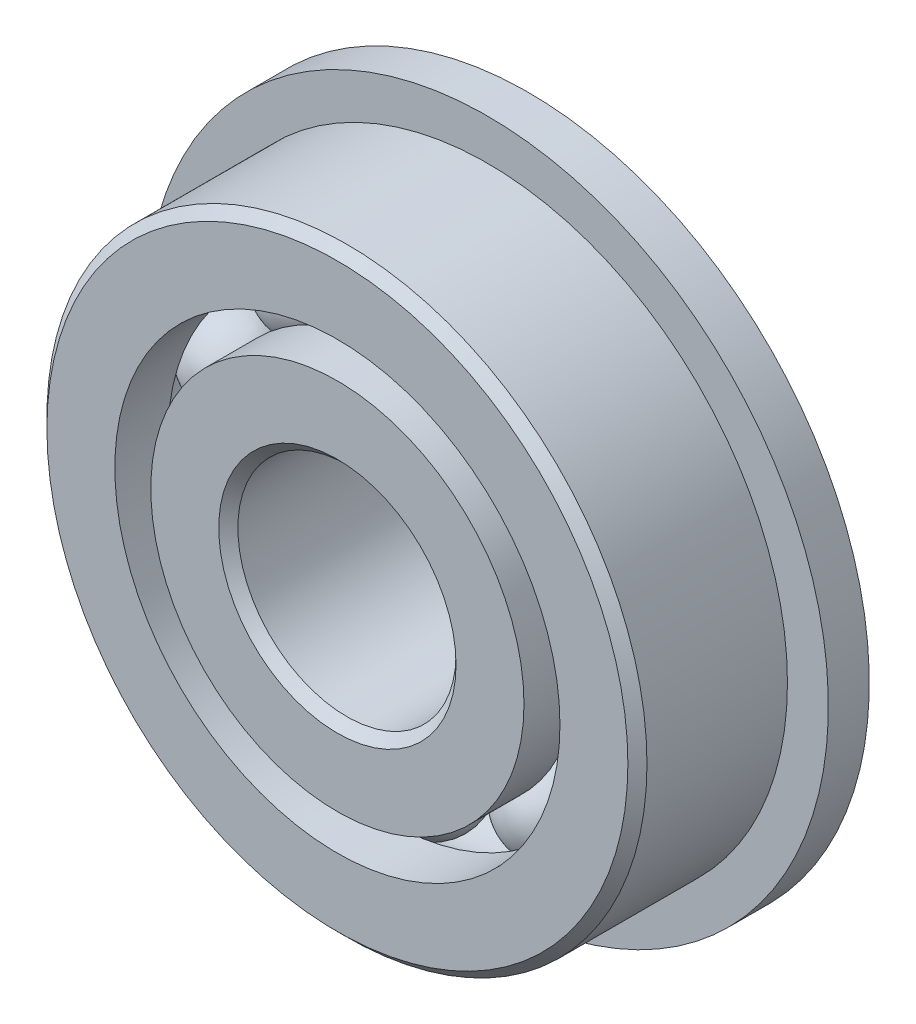
SolidWorks part; units mm, degrees
ref_plane "Front Plane" through (0, 0, 0) normal (0, 0, 1) x (1, 0, 0)
ref_plane "Top Plane" through (0, 0, 0) normal (0, 1, 0) x (1, 0, 0)
ref_plane "Right Plane" through (0, 0, 0) normal (1, 0, 0) x (0, 0, -1)
sketch "Sketch1" plane through (0, 0, 0) normal (1, 0, 0) x (0, 0, -1)
  line L0 (-3.5, 0) -> (3.5, 0) construction
  line L1 (0, 11) -> (0, -11) construction
  line L2 (3.15, 11) -> (-3.15, 11)
  line L3 (-3.15, 11) -> (-3.5, 10.65)
  line L4 (-3.5, 10.65) -> (-3.5, 8.1593)
  line L5 (-3.5, 8.1593) -> (-1.5556, 8.1593)
  line L6 (3.5, 8.1593) -> (1.5556, 8.1593)
  line L7 (3.5, 10.65) -> (3.5, 8.1593)
  line L8 (3.15, 11) -> (3.5, 10.65)
  line L9 (0, 11) -> (0, 7.5) construction
  line L10 (0, 7.5) -> (0, 4) construction
  arc A0 (-1.5556, 8.1593) -> (1.5556, 8.1593) centre (0, 7.5) cw
  point P14 (0, 4)
  dimension "Width" = 7
  dimension "OD" = 22
  dimension "D1" = 45
  dimension "D2" = 0.35
  dimension "Shaft Dia" = 8
  dimension "D3" = 3.1111
  dimension "D4" = 0.6593
revolve "Revolve1" add sketch "Sketch1" angle 360 about L0
sketch "Sketch3" plane through (0, 0, 0) normal (1, 0, 0) x (0, 0, -1)
  line L0 (-3.5, 6.8407) -> (-1.5556, 6.8407)
  line L1 (0, 11) -> (0, -11) construction
  line L2 (-3.5, 10.65) -> (-3.5, 8.1593) construction
  line L3 (-3.5, 6.8407) -> (-3.5, 4.35)
  line L4 (-3.15, 11) -> (-3.5, 10.65) construction
  line L5 (-3.5, 4.35) -> (-3.15, 4)
  line L6 (-3.15, 4) -> (3.15, 4)
  line L7 (3.15, 11) -> (3.15, -11) construction
  line L8 (3.15, 4) -> (3.5, 4.35)
  line L9 (3.5, -10.65) -> (3.5, 10.65) construction
  line L10 (3.5, 4.35) -> (3.5, 6.8407)
  line L11 (3.5, 6.8407) -> (1.5556, 6.8407)
  line L13 (3.15, 11) -> (3.5, 10.65) construction
  arc A0 (1.5556, 8.1593) -> (-1.5556, 8.1593) centre (0, 7.5) ccw construction
  arc A1 (1.5556, 6.8407) -> (-1.5556, 6.8407) centre (0, 7.5) cw
revolve "Revolve3" add sketch "Sketch3" angle 360 about L0
sketch "Sketch4" plane through (0, 0, 0) normal (1, 0, 0) x (0, 0, -1)
  line L0 (-1.6895, 7.5) -> (1.6895, 7.5)
  arc A2 (-1.6895, 7.5) -> (1.6895, 7.5) centre (0, 7.5) cw
  arc A3 (1.5556, 8.1593) -> (-1.5556, 8.1593) centre (0, 7.5) ccw construction
revolve "Revolve4" add sketch "Sketch4" angle 360 about L0
ref_axis "Axis1" through (0, 0, -3.5) along (0, 0, 1)
pattern_circular "CirPattern1" count 10 every 36 about axis through (0, 0, -3.5) along (0, 0, 1) of bodies 104
sketch "Sketch5" plane through (0, 0, 0) normal (1, 0, 0) x (0, 0, -1)
  line L0 (-3.5, 8.1593) -> (-1.5556, 8.1593) construction
  line L1 (-3.325, 8.1593) -> (-1.6895, 8.1593)
  line L2 (-3.325, 8.1593) -> (-3.325, 6.8407)
  line L3 (-3.325, 6.8407) -> (-1.6895, 6.8407)
  line L4 (-1.6895, 8.1593) -> (-1.6895, 6.8407)
  line L5 (-3.5, 6.8407) -> (-1.5556, 6.8407) construction
  line L6 (3.5, 8.1593) -> (1.5556, 8.1593) construction
  line L7 (3.325, 8.1593) -> (1.6895, 8.1593)
  line L8 (3.325, 8.1593) -> (3.325, 6.8407)
  line L9 (3.325, 6.8407) -> (1.6895, 6.8407)
  line L10 (1.6895, 8.1593) -> (1.6895, 6.8407)
  line L11 (3.5, 6.8407) -> (1.5556, 6.8407) construction
  line L12 (-3.15, 11) -> (-3.5, 10.65) construction
  point P18 (-3.325, 10.825)
revolve "Revolve5" [suppressed] add sketch "Sketch5" angle 360 about L0
sketch "Sketch6" plane through (0, 0, 0) normal (1, 0, 0) x (0, 0, -1)
  line L0 (3.5, 0) -> (-3.5, 0) construction
  line L1 (3.5, 8.1593) -> (2, 8.1593)
  line L2 (3.5, 8.1593) -> (3.5, 12.5)
  line L3 (3.5, 12.5) -> (2, 12.5)
  line L4 (2, 8.1593) -> (2, 12.5)
  dimension "Th" = 1.5
  dimension "Flange OD" = 25
revolve "Revolve6" add sketch "Sketch6" angle 360 about L0
equation "\"D2@Sketch1\" = \"Width@Sketch1\"*.05"
equation "\"D3@Sketch1\" = \"Width@Sketch1\"/2.25"
equation "\"D4@Sketch1\" = (((\"OD@Sketch1\"-\"Width@Sketch1\")/2)/3.25)/3.5"
equation "\"D2@CirPattern1\" = 360/\"Balls@CirPattern1\""
